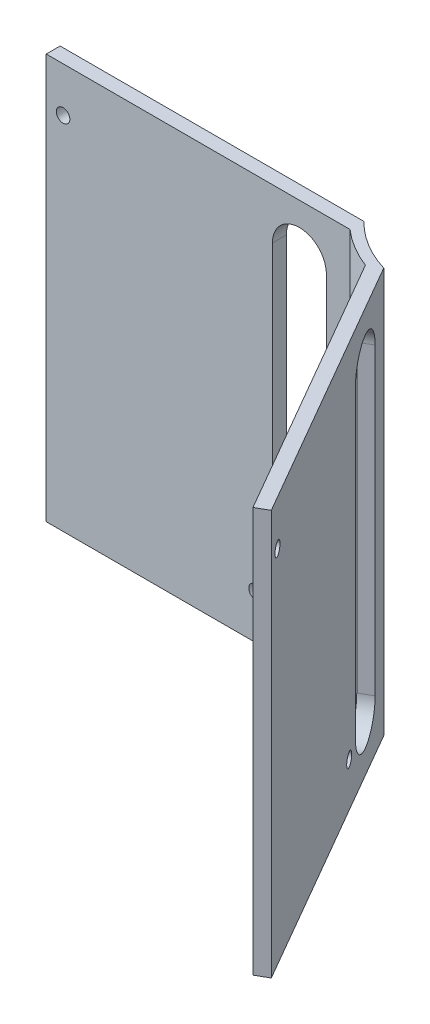
SolidWorks part; units mm, degrees
ref_plane "Plan de face" through (0, 0, 0) normal (0, 0, 1) x (1, 0, 0)
ref_plane "Plan de dessus" through (0, 0, 0) normal (0, 1, 0) x (1, 0, 0)
ref_plane "Plan de droite" through (0, 0, 0) normal (1, 0, 0) x (0, 0, -1)
sketch "Esquisse3" plane through (0, 0, 0) normal (0, 1, 0) x (1, 0, 0)
  line L0 (-150.1573, 0) -> (189.6273, 0) construction
  line L1 (-83.8395, -145.9242) -> (87.7229, 151.2306) construction
  line L2 (-78.0725, 135.2255) -> (117.7517, -203.9519) construction
  line L3 (-125, 131.2995) -> (-125, -153.5705) construction
  line L4 (-25, -24.4949) -> (-115, -24.4949)
  line L6 (-21.2883, 25.5051) -> (-23.9685, 25.5051)
  line L7 (-115, -24.4949) -> (-115, 25.5051)
  line L8 (-25, -24.4949) -> (-115, 25.5051) construction
  line L9 (-21.2883, 25.5051) -> (-115, -24.4949) construction
  line L10 (-23.9685, 25.5051) -> (-115, 25.5051)
  line L11 (34.0723, 8.0048) -> (79.5881, 86.8404)
  line L12 (36.2868, 111.8404) -> (79.5881, 86.8404)
  line L13 (-8.7132, 33.8981) -> (36.2868, 111.8404)
  line L14 (-10.1038, -33.5099) -> (35.4119, -112.3455)
  line L15 (78.7132, -87.3455) -> (35.4119, -112.3455)
  line L16 (33.7132, -9.4032) -> (78.7132, -87.3455)
  line L17 (-23.9685, 25.5051) -> (-25, -24.4949)
  line L18 (-8.7132, 33.8981) -> (34.0723, 8.0048)
  line L19 (-10.1038, -33.5099) -> (33.7132, -9.4032)
  line L20 (-25, -28.6182) -> (-115, -28.6182)
  line L21 (-115, -28.6182) -> (-115, -24.4949)
  line L22 (-13.5526, -35.5011) -> (31.9631, -114.3367)
  line L23 (31.9631, -114.3367) -> (35.4119, -112.3455)
  circle A0 centre (0, 0) radius 125
  circle A1 centre (0, 0) radius 35
  circle A2 centre (0, 0) radius 125
  circle A3 centre (0, 0) radius 125
  circle A4 centre (0, 0) radius 38
  point P9 (-69.0908, 0)
  point P32 (0, 0)
  dimension "D1" = 250
  dimension "D4" = 70
  dimension "D2" = 120
  dimension "D3" = 120
  dimension "D5" = 10
  dimension "D6" = 50
  dimension "D7" = 90
  dimension "D9" = 3
  dimension "D8" = 3
extrude "Boss.-Extru.1" add sketch "Esquisse3" along normal blind 120 contours A4 L4 L21 L20 | L4 A4 L14 A1 | A4 L22 L23 L14 region at (-18.6168, 0, 30.8794) region at (-71.0566, 0, 26.5723) region at (11.4638, 0, 74.8797)
sketch "Esquisse4" plane through (0, 0, 28.6182) normal (0, 0, 1) x (1, 0, 0)
  line L0 (-40, 120) -> (-40, 0) construction
  line L1 (-25, 120) -> (-115, 120) construction
  line L2 (-25, 0) -> (-115, 0) construction
  line L3 (-48, 105) -> (-48, 15)
  line L4 (-25, 120) -> (-25, 0) construction
  line L5 (-115, 60) -> (-20.315, 60) construction
  line L6 (-115, 120) -> (-115, 0) construction
  line L7 (-32, 105) -> (-32, 15)
  arc A0 (-48, 15) -> (-32, 15) centre (-40, 15) ccw
  arc A1 (-48, 105) -> (-32, 105) centre (-40, 105) cw
  dimension "D1" = 8
  dimension "D2" = 15
  dimension "D3" = 45
  dimension "D4" = 45
extrude "Enlèv. mat.-Extru.1" cut sketch "Esquisse4" against normal through all
sketch "Esquisse5" plane through (-25.5369, 0, 14.7437) normal (-0.866, 0, 0.5) x (0.5, 0, 0.866)
  line L0 (38.9685, 120) -> (38.9685, 0) construction
  line L1 (23.9685, 120) -> (115, 120) construction
  line L2 (46.9685, 105) -> (46.9685, 15)
  line L3 (38.9685, 60) -> (127.8483, 60) construction
  line L4 (115, 120) -> (115, 0) construction
  line L5 (23.9685, 120) -> (23.9685, 0) construction
  line L6 (30.9685, 105) -> (30.9685, 15)
  arc A0 (46.9685, 15) -> (30.9685, 15) centre (38.9685, 15) cw
  arc A1 (46.9685, 105) -> (30.9685, 105) centre (38.9685, 105) ccw
  point P14 (115, 60)
  dimension "D1" = 8
  dimension "D2" = 45
  dimension "D3" = 45
  dimension "D4" = 15
extrude "Enlèv. mat.-Extru.2" cut sketch "Esquisse5" against normal through all
sketch "Esquisse6" plane through (0, 0, 28.6182) normal (0, 0, 1) x (1, 0, 0)
  circle A0 centre (-110, 106.75) radius 2 construction
  circle A1 centre (-110, 106.75) radius 2
sketch "Esquisse7" plane through (-25.5369, 0, 14.7437) normal (-0.866, 0, 0.5) x (0.5, 0, 0.866)
  circle A0 centre (110, 106.75) radius 2 construction
  circle A1 centre (110, 106.75) radius 2
extrude "Enlèv. mat.-Extru.3" cut sketch "Esquisse6" against normal through all
extrude "Enlèv. mat.-Extru.4" cut sketch "Esquisse7" against normal through all
sketch "Esquisse8" plane through (0, 0, 28.6182) normal (0, 0, 1) x (1, 0, 0)
  circle A0 centre (-53, 13) radius 2 construction
  circle A1 centre (-53, 13) radius 2
sketch "Esquisse9" plane through (-25.5369, 0, 14.7437) normal (-0.866, 0, 0.5) x (0.5, 0, 0.866)
  circle A0 centre (51.9685, 13) radius 2 construction
  circle A1 centre (51.9685, 13) radius 2
extrude "Enlèv. mat.-Extru.5" cut sketch "Esquisse8" against normal through all
extrude "Enlèv. mat.-Extru.6" cut sketch "Esquisse9" against normal through all
